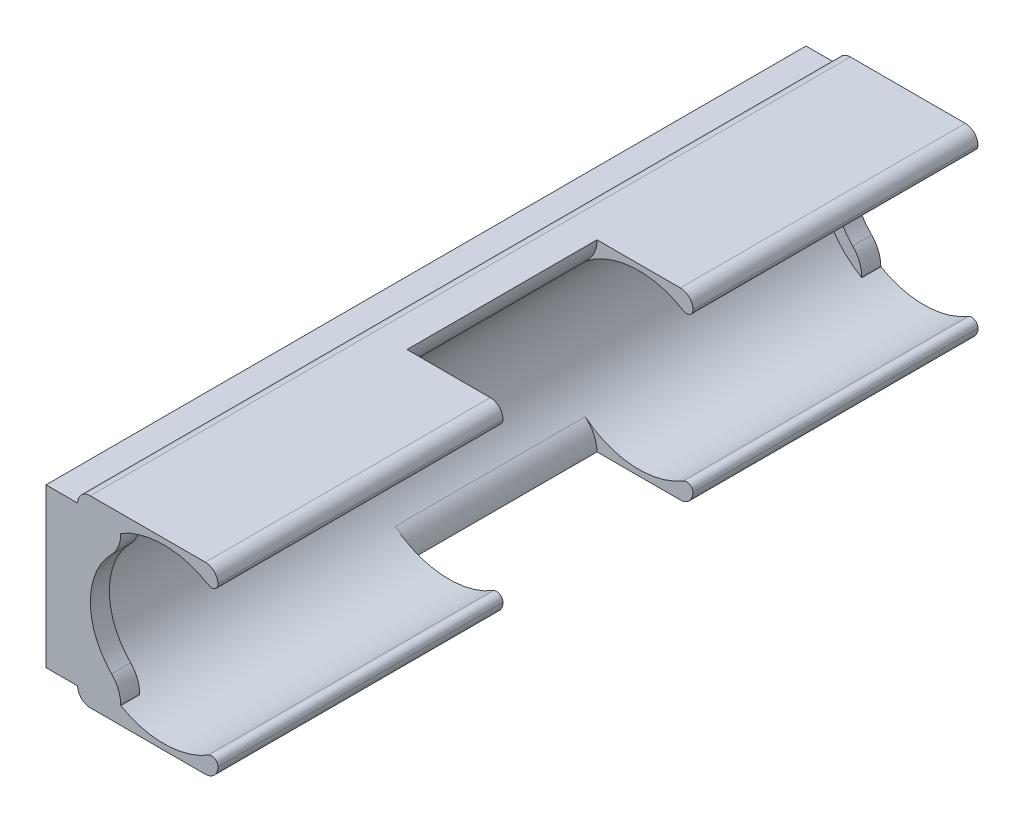
SolidWorks part; units mm, degrees
ref_plane "Front Plane" through (0, 0, 0) normal (0, 0, 1) x (1, 0, 0)
ref_plane "Top Plane" through (0, 0, 0) normal (0, 1, 0) x (1, 0, 0)
ref_plane "Right Plane" through (0, 0, 0) normal (1, 0, 0) x (0, 0, -1)
sketch "Sketch1" plane through (0, 0, 0) normal (1, 0, 0) x (0, 0, -1)
  line L1 (0, 0) -> (120, 0)
  line L2 (0, 0) -> (0, 25)
  line L3 (0, 25) -> (120, 25)
  line L4 (120, 0) -> (120, 25)
  dimension "D1" = 25
  dimension "D2" = 120
extrude "Base" add sketch "Sketch1" along normal blind 5
sketch "Sketch2" plane through (0, 0, 0) normal (0, 0, 1) x (1, 0, 0)
  line L0 (5, 25) -> (5, 0) construction
  line L1 (5, 25) -> (5, 0) construction
  line L2 (5, 12.5) -> (32.2, 12.5) construction
  line L5 (7, 27) -> (25.151, 27)
  line L6 (27.151, 23.0755) -> (27.151, 25)
  line L7 (7, -2) -> (25.151, -2)
  line L8 (27.151, 1.9245) -> (27.151, 0)
  line L9 (5, 0) -> (5, 25)
  circle A0 centre (18.6, 12.5) radius 13.6
  arc A1 (5, 25) -> (7, 27) centre (7, 25) cw
  arc A2 (25.151, 27) -> (27.151, 25) centre (25.151, 25) cw
  arc A3 (5, 0) -> (7, -2) centre (7, 0) ccw
  arc A4 (25.151, -2) -> (27.151, 0) centre (25.151, 0) ccw
  point P2 (5, 12.5)
  point P15 (7, 25)
  point P18 (27.151, 27)
  line M8 (5, 0) -> (5, 25)
  dimension "D1" = 27.2
  dimension "D4" = 2
  dimension "D5" = 2
  dimension "D2" = 20.25
  dimension "D3" = 2
extrude "Clip" add sketch "Sketch2" against normal up to surface (120 mm away) contours A2 L5 A1 A0 L6 M8 | L7 A4 L8 A0 A3 M8 region at (16.0755, 26.7353, 0) region at (12.6265, -0.0119, 0) up to face at (2.5, 12.5, -120)
sketch3d "3DSketch1"
  line L0 (0, 25, -120) -> (0, 25, 0) construction
  line L1 (0, 0, 0) -> (0, 0, -120) construction
  point P0 (0, 25, -60)
  point P1 (0, 0, -60)
ref_plane "Plane2" through (0, 0, -60) normal (0, 0, -1) x (-1, 0, 0)
sketch "Sketch3" plane through (0, 0, 0) normal (-1, 0, 0) x (0, 0, 1)
  line L0 (-120, 0) -> (-120, 25) construction
  line L1 (-60, 13.75) -> (-60, -13.75) construction
  circle A0 centre (-100, 12.5) radius 1.5
  circle A1 centre (-20, 12.5) radius 1.5
  point P4 (-120, 12.5)
  dimension "D1" = 3
  dimension "D2" = 20
extrude "ScrewHoles" cut sketch "Sketch3" against normal blind 3
sketch "Sketch4" plane through (0, 0, 0) normal (0, 0, 1) x (1, 0, 0)
  line L2 (18.6, 12.5) -> (5, 12.5)
  line L4 (11.8, 0.7221) -> (11.8, 0.8244)
  line L6 (11.8, 24.1756) -> (11.8, 24.2779)
  arc A1 (10.3542, 20.6589) -> (10.3542, 4.3411) centre (18.6, 12.5) ccw
  arc A2 (27.151, 23.0755) -> (27.151, 1.9245) centre (18.6, 12.5) ccw construction
  arc A3 (11.8, 24.2779) -> (11.8, 0.7221) centre (18.6, 12.5) ccw
  arc A4 (10.3542, 4.3411) -> (11.8, 0.8244) centre (6.8, 0.8244) cw
  arc A5 (10.3542, 20.6589) -> (11.8, 24.1756) centre (6.8, 24.1756) ccw
  point P11 (11.8, 12.5)
  point P15 (5, 12.5)
  point P18 (18.6, 12.5)
  point P20 (11.8, 3.1021)
  point P23 (11.8, 21.8979)
  dimension "D1" = 2
  dimension "D2" = 5
extrude "ClipWall" add sketch "Sketch4" against normal blind 3 contours A1 A4 L4 A3 L6 A5
mirror "Mirror1" about plane through (0, 0, -60) normal (0, 0, -1) of "ClipWall"
fillet "RoundedCorners" radius 1 2 edges at (27.151, 1.9245, -60) (27.151, 23.0755, -60)
sketch "Sketch5" plane through (0, 0, -60) normal (0, 0, -1) x (-1, 0, 0)
  line L1 (-27.151, 27) -> (-12, 27)
  line L2 (-27.151, 27) -> (-27.151, -2)
  line L3 (-27.151, -2) -> (-12, -2)
  line L4 (-12, 27) -> (-12, -2)
  line L6 (-25.151, -2) -> (-7, -2) construction
  line L7 (-25.151, 27) -> (-7, 27) construction
  dimension "D1" = 5
extrude "FingerGap" cut sketch "Sketch5" against normal mid plane 30
fillet "FingerGroove" radius 5 2 edges at (12, 0.6088, -60) (12, 24.3912, -60)
